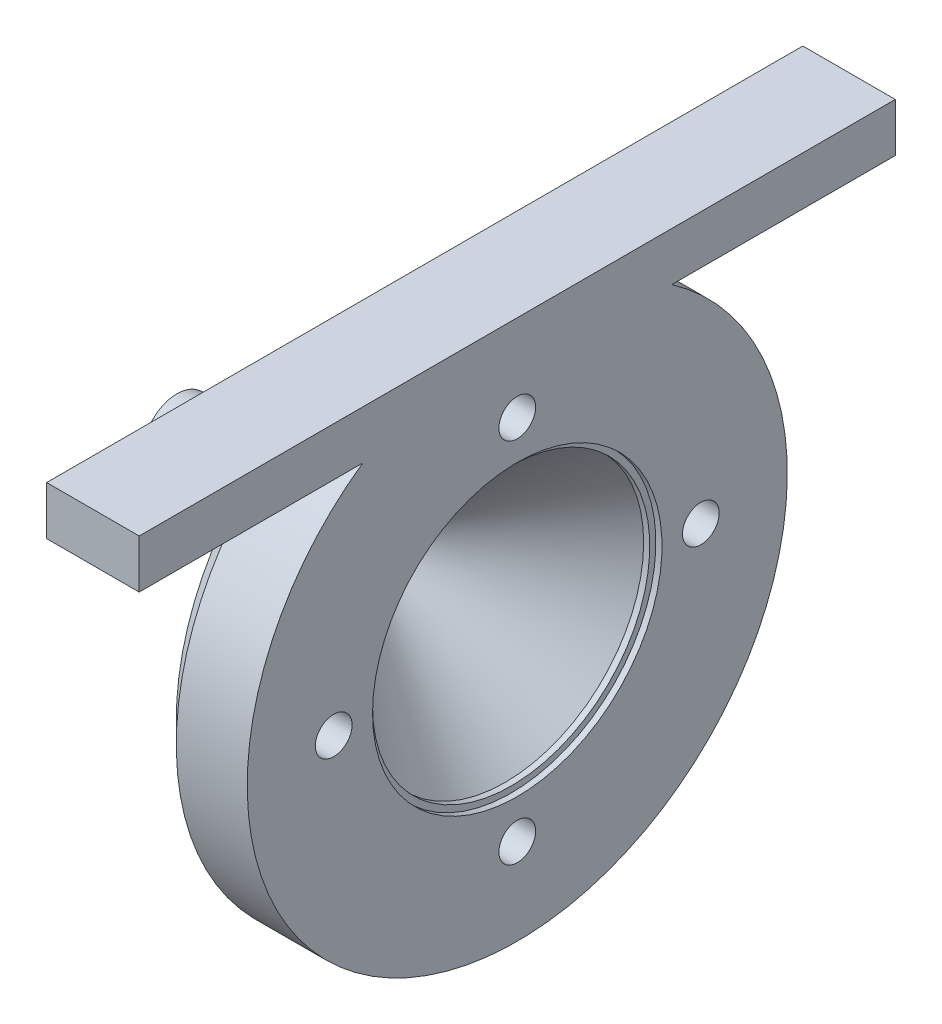
SolidWorks part; units mm, degrees
ref_plane "Front Plane" through (0, 0, 0) normal (0, 0, 1) x (1, 0, 0)
ref_plane "Top Plane" through (0, 0, 0) normal (0, 1, 0) x (1, 0, 0)
ref_plane "Right Plane" through (0, 0, 0) normal (1, 0, 0) x (0, 0, -1)
sketch "Sketch1" plane through (0, 0, 0) normal (0, 0, 1) x (1, 0, 0)
  line L0 (-801.9206, 0) -> (36107.5283, 0) construction
  line L3 (-14.0102, 3.8) -> (-14.0102, 3.15)
  line L8 (-18.3435, 1.9) -> (0, 1.9)
  line L9 (-18.3435, 1.9) -> (-18.3435, 3.15)
  line L10 (13.1623, 13.4) -> (13.1623, 25)
  line L12 (13.1623, 25) -> (4.5963, 25)
  line L16 (13.1623, 13.4) -> (12.5963, 13.4)
  line L17 (12.5963, 13.4) -> (12.5963, 12.834)
  line L18 (4.5963, 25) -> (4.5963, 12.834)
  line L20 (0, 1.9) -> (12.0303, 12.834)
  line L21 (-18.3435, 3.15) -> (-14.0102, 3.8)
  line L22 (12.0303, 12.834) -> (12.5963, 12.834)
  line L23 (-14.0102, 3.15) -> (-9.6768, 3.8)
  line L25 (-9.6768, 3.15) -> (-5.3435, 3.8)
  line L26 (-9.6768, 3.8) -> (-9.6768, 3.15)
  line L27 (-5.3435, 3.8) -> (4.5963, 12.834)
  line L28 (4.5963, 20.5) -> (13.1623, 20.5)
  point P14 (12.8591, 20.5)
  point P17 (13.1623, 20.5)
  dimension "D3" = 0.566
  dimension "D2" = 7.6
  dimension "D6" = 3.8
  dimension "D7" = 6.3
  dimension "D5" = 25
  dimension "D8" = 13.4
  dimension "D10" = 0.566
  dimension "D4" = 5
  dimension "D9" = 0.566
  dimension "D11" = 13
  dimension "D12" = 8.566
  dimension "D13" = 4.5
revolve "Revolve17" add sketch "Sketch1" angle 360 about L0
sketch "Sketch4" plane through (4.5963, 0, 0) normal (-1, 0, 0) x (0, 0, 1)
  circle A0 centre (0, 0) radius 16.9947 construction
  point P3 (0, 16.9947)
  point P7 (16.9947, 0)
  point P12 (-16.9947, 0)
  point P13 (0, -16.9947)
hole_wizard "M3 Clearance Hole1" positions "Sketch4" profile "Sketch5" hole size "M3" standard "ISO"
sketch "Sketch5" plane through (4.5963, -16.9947, 0) normal (0, 1, 0) x (0, 0, 1)
  line L0 (0, 0) -> (0, 9.5875)
  line L1 (0, 9.5875) -> (1.7, 8.566)
  line L2 (1.7, 8.566) -> (1.7, 0)
  line L5 (1.7, 0) -> (0, 0)
  line L10 (0, 9.5875) -> (-1.7, 8.566) construction
  line L11 (0, -6.35) -> (0, 107.95) construction
  dimension "Hole Dia." = 3.4
  dimension "Hole Depth" = 8.566
  dimension "Drill Angle" = 118
chamfer "Chamfer1" distance 2 angle 45 1 edges at (4.5963, 0, 25)
extrude "Boss-Extrude1" add sketch "Sketch1<11>" against normal mid plane 70 contours L18 L28 L10 L12 region at (8.8793, 22.75, 0)
sketch "Sketch1<11>" plane through (0, 0, 0) normal (0, 0, 1) x (1, 0, 0) same geometry as "Sketch1"
sketch "Sketch9" plane through (0, 20.5, 0) normal (0, -1, 0) x (-1, 0, 0)
  line L0 (-4.5963, -35) -> (-13.1623, 35) construction
  line L1 (-4.5963, -10.4283) -> (-4.5963, -35) construction
  line L2 (-4.5963, -35) -> (-13.1623, -35) construction
  line L3 (-13.1623, 35) -> (-13.1623, 14.3091) construction
  line L4 (-13.1623, 35) -> (-4.5963, 35) construction
  line L5 (-4.5963, 35) -> (-13.1623, 35) construction
  line L6 (-4.5963, 35) -> (-13.1623, -35) construction
  line L7 (-13.1623, -14.3091) -> (-13.1623, -35) construction
  line L8 (-8.8793, -35) -> (-8.8793, 35) construction
  circle A0 centre (-8.8793, -31) radius 1.7
  point P18 (0, 0)
  dimension "D1" = 3.4
  dimension "D2" = 4
equation "\"D10@Sketch1\"=\"D3@Sketch1\""
equation "\"D9@Sketch1\"=\"D3@Sketch1\""
